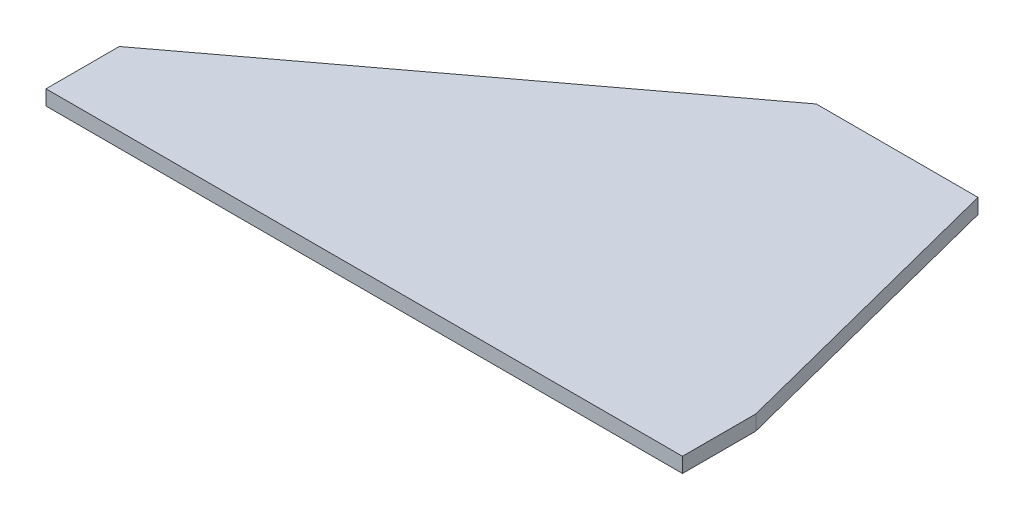
SolidWorks part; units mm, degrees
ref_plane "Front Plane" through (0, 0, 0) normal (0, 0, 1) x (1, 0, 0)
ref_plane "Top Plane" through (0, 0, 0) normal (0, 1, 0) x (1, 0, 0)
ref_plane "Right Plane" through (0, 0, 0) normal (1, 0, 0) x (0, 0, -1)
sketch "Sketch1" plane through (0, 0, 0) normal (0, 1, 0) x (1, 0, 0)
  line L0 (0, 0) -> (0, 23.368)
  line L1 (0, 23.368) -> (127, 118.618)
  line L2 (127, 118.618) -> (178.562, 118.618)
  line L3 (178.562, 118.618) -> (202.946, 23.368)
  line L4 (202.946, 23.368) -> (202.946, 0)
  line L5 (202.946, 0) -> (0, 0)
  line L6 (0, 23.368) -> (0, 118.618) construction
  line L7 (0, 118.618) -> (127, 118.618) construction
  dimension "D1" = 202.946
  dimension "D2" = 23.368
  dimension "D3" = 51.562
  dimension "D4" = 95.25
  dimension "D5" = 127
extrude "Boss-Extrude1" add sketch "Sketch1" along normal blind 2.3813 and the other way blind 2.3813 contours L3 L4 L5 L0 L1 L2
equation "\"Root Chord\"=7.99"
equation "\"Tip Chord\"=2.03"
equation "\"Height\"=3.75"
equation "\"Sweep Length\"=5"
equation "\"Fin Thickness\"= 3 / 16"
equation "\"Bevel Depth\"= 1 / 16"
equation "\"Bevel Width\"= 1 / 4"
equation "\"Tab Height\"=0.92"
equation "\"D2@Sketch1\"=\"Tab Height\""
equation "\"D4@Sketch1\"=\"Height\""
equation "\"D5@Sketch1\"=\"Sweep Length\""
equation "\"D3@Sketch1\"=\"Tip Chord\""
equation "\"D1@Sketch1\"=\"Root Chord\""
equation "\"D1@Boss-Extrude1\"=\"Fin Thickness\"/2"
equation "\"D2@Boss-Extrude1\"=\"Fin Thickness\"/2"
equation "\"D1@Chamfer2\"=\"Bevel Depth\""
equation "\"D3@Chamfer2\"=\"Bevel Width\""
